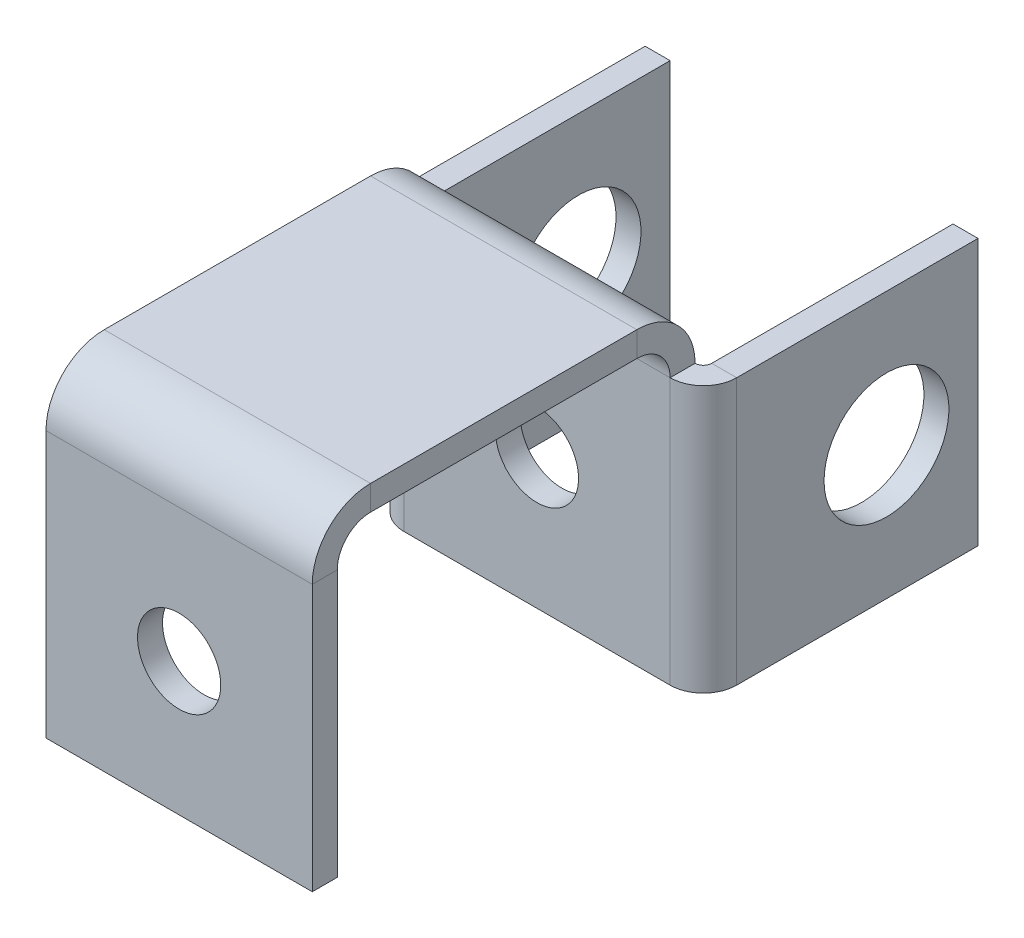
SolidWorks part; units mm, degrees
note: The reader was unsure of these and kept them because the rebuilt part matched: flange length of "Kenar-Flanş1", "Kenar-Flanş2", "Kenar-Flanş3", "Kenar-Flanş4".
ref_plane "Ön Düzlem" through (0, 0, 0) normal (0, 0, 1) x (1, 0, 0)
ref_plane "Üst Düzlem" through (0, 0, 0) normal (0, 1, 0) x (1, 0, 0)
ref_plane "Sağ Düzlem" through (0, 0, 0) normal (1, 0, 0) x (0, 0, -1)
sketch "Sketch1" plane through (0, 0, 0) normal (0, 0, 1) x (1, 0, 0)
  line L1 (-16, -16) -> (16, -16)
  line L2 (-16, -16) -> (-16, 16)
  line L3 (-16, 16) -> (16, 16)
  line L4 (16, -16) -> (16, 16)
  line L5 (-16, -16) -> (16, 16) construction
  line L6 (-16, 16) -> (16, -16) construction
  point P0 (0, 0)
  dimension "D1" = 32
base flange "Base-Flange1" sketch "Sketch1" thickness 3 reverse thickness direction no parameters "D1"=0.7366
edge flange "Kenar-Flanş1" sketch "Sketch8" flange angle 90 flange length 39 flange position bend outside bend radius 4 thickness 3 relief rectangular parameters "D6"=10
sketch "Sketch8" plane through (0, 16, 0) normal (0, 1, 0) x (-1, 0, 0)
  line L2 (-16, 0) -> (-16, 36)
  line L3 (-16, 36) -> (16, 36)
  line L4 (16, 36) -> (16, 0)
  line L7 (-16, 0) -> (16, 0) construction
  line L8 (-16, 0) -> (16, 0)
bend "KenarBükümü1" bend radius 4 bend angle 90 parameters "D5"=1
edge flange "Kenar-Flanş2" sketch "Sketch13" flange angle 90 flange length 39 flange position bend outside bend radius 4 thickness 3 relief rectangular parameters "D6"=10
sketch "Sketch13" plane through (0, 20, 36) normal (0, 0, 1) x (-1, 0, 0)
  line L0 (16, 0) -> (-16, 0) construction
  line L1 (16, 0) -> (-16, 0)
  line L2 (-16, 0) -> (-16, 36)
  line L3 (-16, 36) -> (16, 36)
  line L4 (16, 36) -> (16, 0)
bend "KenarBükümü2" bend radius 4 bend angle 90 parameters "D5"=2
edge flange "Kenar-Flanş3" sketch "Sketch16" flange angle 90 flange length 33 flange position bend outside bend radius 1 thickness 3 relief rectangular parameters "D6"=10
sketch "Sketch16" plane through (-16, 0, -3) normal (-1, 0, 0) x (0, 1, 0)
  line L0 (16, 0) -> (-16, 0) construction
  line L1 (16, 0) -> (-16, 0)
  line L2 (-16, 0) -> (-16, 30)
  line L3 (-16, 30) -> (16, 30)
  line L4 (16, 30) -> (16, 0)
bend "KenarBükümü3" bend radius 1 bend angle 90 parameters "D5"=3
edge flange "Kenar-Flanş4" sketch "Sketch19" flange angle 90 flange length 33 flange position bend outside bend radius 1 thickness 3 relief rectangular parameters "D6"=10
sketch "Sketch19" plane through (16, 0, -3) normal (1, 0, 0) x (0, -1, 0)
  line L0 (16, 0) -> (-16, 0) construction
  line L1 (16, 0) -> (-16, 0)
  line L2 (-16, 0) -> (-16, 30)
  line L3 (-16, 30) -> (16, 30)
  line L4 (16, 30) -> (16, 0)
bend "KenarBükümü4" bend radius 1 bend angle 90 parameters "D5"=4
sketch "Sketch20" plane through (0, 0, 43) normal (0, 0, 1) x (1, 0, 0)
  circle A0 centre (0, 0) radius 5
  dimension "D1" = 10
extrude "Cut-Extrude1" cut sketch "Sketch20" against normal through all normal cut yes
sketch "Sketch21" plane through (-20, 0, 0) normal (-1, 0, 0) x (0, 0, 1)
  line L0 (-4, 16) -> (-4, -16) construction
  circle A0 centre (-22, 0) radius 7.5
  point P4 (-4, 0)
  dimension "D1" = 15
  dimension "D2" = 18
extrude "Cut-Extrude2" cut sketch "Sketch21" against normal up to surface and the other way through all up to face at (20, 0, -18.5)
sketch "Büküm-Çizgileri1" [suppressed] plane through (0, 0, 0) normal (0, 1, 0) x (1, 0, 0)
sketch "Sınırlandırma-Kutusu1" [suppressed] plane through (0, 0, 0) normal (0, 1, 0) x (1, 0, 0)
sheet metal parameters "Sac-Levha1" thickness 3 parameters "D1"=0.7366
flat pattern "Düz-Çoğaltma1" [suppressed]
sketch "Büküm-Çizgileri2" plane through (0, 0, 0) normal (0, 1, 0) x (1, 0, 0)
sketch3d "Sınırlandırma-Kutusu2" [suppressed]
  line L0 (16, -16, 0) -> (-16, -16, 0) construction
  line L1 (16, 16, 0) -> (-16, 16, 0) construction
  line L2 (16, -16, 0) -> (16, 16, 0) construction
  line L3 (-16, -16, 0) -> (-16, 16, 0) construction
sheet metal parameters "Sac-Levha2" thickness 3 parameters "D1"=0.7366
flat pattern "Düz-Çoğaltma1"
sketch "Büküm-Çizgileri2" plane through (0, 0, 0) normal (0, 0, 1) x (1, 0, 0)
  line L0 (16, 17.9635) -> (-16, 17.9635) construction
  line L1 (16, 17.9635) -> (-16, 17.9635) construction
sketch3d "Sınırlandırma-Kutusu2" [suppressed]
  line L0 (16, 51.927, 0) -> (16, -16, 0) construction
  line L1 (-16, 51.927, 0) -> (-16, -16, 0) construction
  line L2 (16, 51.927, 0) -> (-16, 51.927, 0) construction
  line L3 (16, -16, 0) -> (-16, -16, 0) construction
bend of the flat pattern "Düzleştirme TipiKenarBükümü1>1"
sheet metal parameters "Sac-Levha3" thickness 3 parameters "D1"=0.7366
flat pattern "Düz-Çoğaltma1"
sketch "Büküm-Çizgileri2" plane through (0, 0, 0) normal (0, 0, 1) x (1, 0, 0)
  line L0 (16, 17.9635) -> (-16, 17.9635) construction
  line L1 (16, 17.9635) -> (-16, 17.9635) construction
  line L2 (16, 53.8905) -> (-16, 53.8905) construction
  line L3 (16, 53.8905) -> (-16, 53.8905) construction
sketch3d "Sınırlandırma-Kutusu2" [suppressed]
  line L0 (16, 87.854, 0) -> (16, -16, 0) construction
  line L1 (-16, 87.854, 0) -> (-16, -16, 0) construction
  line L2 (16, 87.854, 0) -> (-16, 87.854, 0) construction
  line L3 (16, -16, 0) -> (-16, -16, 0) construction
bend of the flat pattern "Düzleştirme TipiKenarBükümü1>1"
bend of the flat pattern "Düzleştirme TipiKenarBükümü2>1"
sheet metal parameters "Sac-Levha4" thickness 3 parameters "D1"=0.7366
flat pattern "Düz-Çoğaltma1"
sketch "Büküm-Çizgileri2" plane through (0, 0, 0) normal (0, 0, 1) x (1, 0, 0)
  line L0 (16, 17.9635) -> (-16, 17.9635) construction
  line L1 (16, 17.9635) -> (-16, 17.9635) construction
  line L2 (16, 53.8905) -> (-16, 53.8905) construction
  line L3 (16, 53.8905) -> (-16, 53.8905) construction
  line L4 (-17.9635, 16) -> (-17.9635, -16) construction
  line L5 (-17.9635, 16) -> (-17.9635, -16) construction
sketch3d "Sınırlandırma-Kutusu2" [suppressed]
  line L0 (16, 87.854, 0) -> (16, -16, 0) construction
  line L1 (-48.927, 87.854, 0) -> (-48.927, -16, 0) construction
  line L2 (16, 87.854, 0) -> (-48.927, 87.854, 0) construction
  line L3 (16, -16, 0) -> (-48.927, -16, 0) construction
bend of the flat pattern "Düzleştirme TipiKenarBükümü1>1"
bend of the flat pattern "Düzleştirme TipiKenarBükümü2>1"
bend of the flat pattern "Düzleştirme TipiKenarBükümü3>1"
sheet metal parameters "Sac-Levha5" thickness 3 parameters "D1"=0.7366
flat pattern "Düz-Çoğaltma1"
sketch "Büküm-Çizgileri2" plane through (0, 0, 0) normal (0, 0, 1) x (1, 0, 0)
  line L0 (16, 17.9635) -> (-16, 17.9635) construction
  line L1 (16, 17.9635) -> (-16, 17.9635) construction
  line L2 (16, 53.8905) -> (-16, 53.8905) construction
  line L3 (16, 53.8905) -> (-16, 53.8905) construction
  line L4 (-17.9635, 16) -> (-17.9635, -16) construction
  line L5 (-17.9635, 16) -> (-17.9635, -16) construction
  line L6 (17.9635, -16) -> (17.9635, 16) construction
  line L7 (17.9635, -16) -> (17.9635, 16) construction
sketch3d "Sınırlandırma-Kutusu2" [suppressed]
  line L0 (48.927, 87.854, 0) -> (48.927, -16, 0) construction
  line L1 (-48.927, 87.854, 0) -> (-48.927, -16, 0) construction
  line L2 (48.927, 87.854, 0) -> (-48.927, 87.854, 0) construction
  line L3 (48.927, -16, 0) -> (-48.927, -16, 0) construction
bend of the flat pattern "Düzleştirme TipiKenarBükümü1>1"
bend of the flat pattern "Düzleştirme TipiKenarBükümü2>1"
bend of the flat pattern "Düzleştirme TipiKenarBükümü3>1"
bend of the flat pattern "Düzleştirme TipiKenarBükümü4>1"
sheet metal parameters "Sac-Levha6" thickness 3 parameters "D1"=0.7366
flat pattern "Düz-Çoğaltma1"
sketch "Büküm-Çizgileri2" plane through (0, 0, 0) normal (0, 0, 1) x (1, 0, 0)
  line L0 (16, 17.9635) -> (-16, 17.9635) construction
  line L1 (16, 17.9635) -> (-16, 17.9635) construction
  line L2 (16, 53.8905) -> (-16, 53.8905) construction
  line L3 (16, 53.8905) -> (-16, 53.8905) construction
  line L4 (-17.9635, 16) -> (-17.9635, -16) construction
  line L5 (-17.9635, 16) -> (-17.9635, -16) construction
  line L6 (17.9635, -16) -> (17.9635, 16) construction
  line L7 (17.9635, -16) -> (17.9635, 16) construction
sketch3d "Sınırlandırma-Kutusu2" [suppressed]
  line L0 (48.927, 87.854, 0) -> (48.927, -16, 0) construction
  line L1 (-48.927, 87.854, 0) -> (-48.927, -16, 0) construction
  line L2 (48.927, 87.854, 0) -> (-48.927, 87.854, 0) construction
  line L3 (48.927, -16, 0) -> (-48.927, -16, 0) construction
bend of the flat pattern "Düzleştirme TipiKenarBükümü1>1"
bend of the flat pattern "Düzleştirme TipiKenarBükümü2>1"
bend of the flat pattern "Düzleştirme TipiKenarBükümü3>1"
bend of the flat pattern "Düzleştirme TipiKenarBükümü4>1"
sheet metal parameters "Sac-Levha7" thickness 3 parameters "D1"=0.7366
flat pattern "Düz-Çoğaltma1"
sketch "Büküm-Çizgileri2" plane through (0, 0, 0) normal (0, 0, 1) x (1, 0, 0)
  line L0 (16, 20.3197) -> (-16, 20.3197) construction
  line L1 (16, 20.3197) -> (-16, 20.3197) construction
  line L2 (16, 60.9591) -> (-16, 60.9591) construction
  line L3 (16, 60.9591) -> (-16, 60.9591) construction
  line L4 (-17.9635, 16) -> (-17.9635, -16) construction
  line L5 (-17.9635, 16) -> (-17.9635, -16) construction
  line L6 (17.9635, -16) -> (17.9635, 16) construction
  line L7 (17.9635, -16) -> (17.9635, 16) construction
sketch3d "Sınırlandırma-Kutusu2" [suppressed]
  line L0 (48.927, 97.2788, 0) -> (48.927, -16, 0) construction
  line L1 (-48.927, 97.2788, 0) -> (-48.927, -16, 0) construction
  line L2 (48.927, 97.2788, 0) -> (-48.927, 97.2788, 0) construction
  line L3 (48.927, -16, 0) -> (-48.927, -16, 0) construction
bend of the flat pattern "Düzleştirme TipiKenarBükümü1>1"
bend of the flat pattern "Düzleştirme TipiKenarBükümü2>1"
bend of the flat pattern "Düzleştirme TipiKenarBükümü3>1"
bend of the flat pattern "Düzleştirme TipiKenarBükümü4>1"
